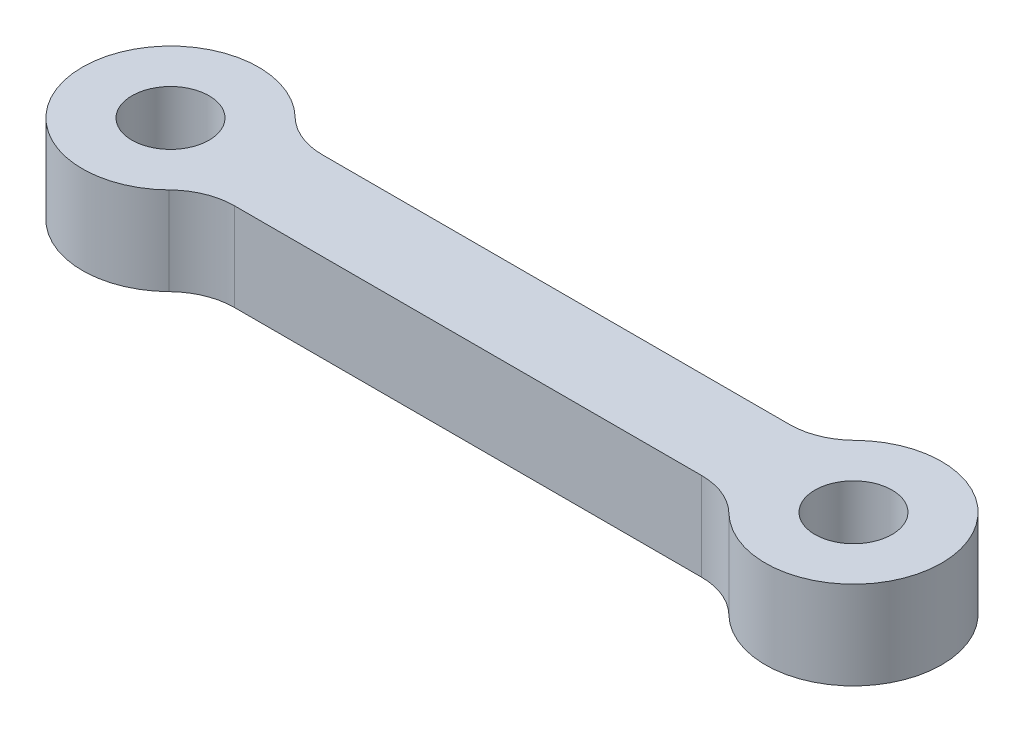
SolidWorks part; units mm, degrees
ref_plane "Front Plane" through (0, 0, 0) normal (0, 0, 1) x (1, 0, 0)
ref_plane "Top Plane" through (0, 0, 0) normal (0, 1, 0) x (1, 0, 0)
ref_plane "Right Plane" through (0, 0, 0) normal (1, 0, 0) x (0, 0, -1)
sketch "Sketch1" plane through (0, 0, 0) normal (0, 1, 0) x (1, 0, 0)
  line L0 (0, 0) -> (31, 0) construction
  line L1 (3.4641, 2) -> (27.5359, 2)
  line L2 (3.4641, -2) -> (27.5359, -2)
  circle A0 centre (0, 0) radius 4
  circle A1 centre (0, 0) radius 1.75
  circle A2 centre (31, 0) radius 1.75
  circle A3 centre (31, 0) radius 4
  dimension "D1" = 3.5
  dimension "D2" = 8
  dimension "D3" = 31
  dimension "D4" = 4
extrude "Boss-Extrude1" add sketch "Sketch1" along normal blind 4 contours A1 A0 | L0 A0 L2 A3 | A0 L0 A3 L1 | A3 A2 region at (3.7544, 0, 1.006) region at (15.5, 0, -1.0075) region at (15.5, 0, 1.0075) region at (27.2456, 0, -1.006)
fillet "Fillet1" radius 3 4 edges at (27.5359, 2, 2) (3.4641, 2, -2) (27.5359, 2, -2) (3.4641, 2, 2)
ref_axis "Axis1" through (31, 10.0997, 0) along (0, -1, 0)
ref_axis "Axis2" through (0, 8.956, 0) along (0, -1, 0)
